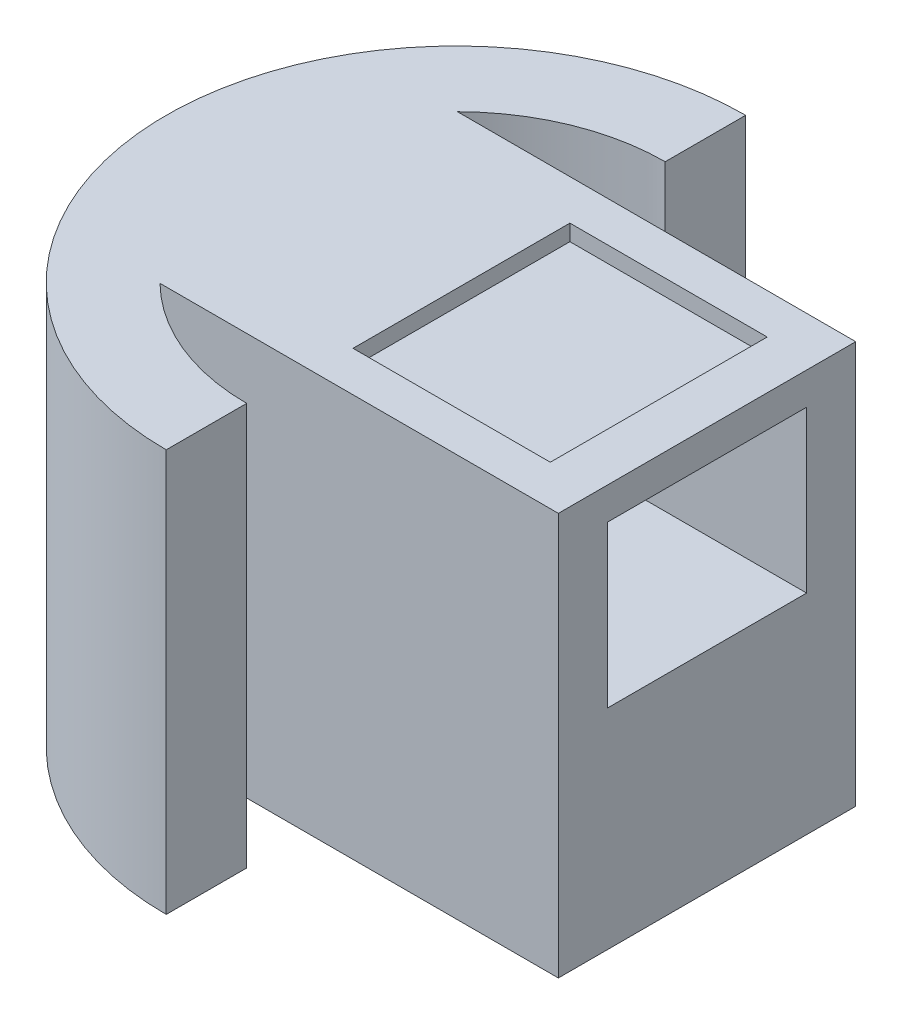
SolidWorks part; units mm, degrees
ref_plane "前基準面" through (0, 0, 0) normal (0, 0, 1) x (1, 0, 0)
ref_plane "上基準面" through (0, 0, 0) normal (0, 1, 0) x (1, 0, 0)
ref_plane "右基準面" through (0, 0, 0) normal (1, 0, 0) x (0, 0, -1)
sketch "草圖1" plane through (0, 0, 0) normal (0, 1, 0) x (1, 0, 0)
  line L0 (0, -1000) -> (0, 49000) construction
  arc A0 (0, 914.4) -> (0, -914.4) centre (0, 0) ccw
  dimension "D1" = 1828.8
extrude "伸長-薄件1" add sketch "草圖1" along normal blind 1270 thin thin type one direction reverse wall 254
sketch "草圖5" plane through (0, 1270, 0) normal (0, 1, 0) x (1, 0, 0)
  line L1 (-864.3979, -163.0846) -> (-792.1626, -163.0846)
  line L2 (-864.3979, -163.0846) -> (-864.3979, 175.7333)
  line L3 (-864.3979, 175.7333) -> (-792.1626, 175.7333)
  line L4 (-792.1626, -163.0846) -> (-792.1626, 175.7333)
extrude "填補1" add sketch "草圖5" against normal through all
sketch "草圖9" plane through (0, 1270, 0) normal (0, 1, 0) x (1, 0, 0)
  line L0 (-792.1626, -1061.7609) -> (-792.1626, 48938.2391) construction
  line L2 (-858.6021, -138.4881) -> (-792.1626, -138.4881)
  line L3 (-858.6021, -138.4881) -> (-858.6021, -258.1826)
  line L4 (-858.6021, -258.1826) -> (-792.1626, -258.1826)
  line L5 (-792.1626, -138.4881) -> (-792.1626, -258.1826)
extrude "填補2" add sketch "草圖9" against normal through all
sketch "第二分類" plane through (0, 0, 0) normal (0, 1, 0) x (1, 0, 0)
  line L1 (-792.4704, 339.6329) -> (792.4704, 339.6329)
  line L2 (-792.4704, 339.6329) -> (-792.4704, -339.6329)
  line L3 (-792.4704, -339.6329) -> (792.4704, -339.6329)
  line L4 (792.4704, 339.6329) -> (792.4704, -339.6329)
  line L5 (-792.4704, 339.6329) -> (792.4704, -339.6329) construction
  line L6 (-792.4704, -339.6329) -> (792.4704, 339.6329) construction
  point P0 (0, 0)
extrude "填料-伸長7" add sketch "第二分類" along normal blind 1270
sketch "草圖15" plane through (792.4704, 0, 0) normal (1, 0, 0) x (0, 0, -1)
  line L0 (-339.6329, 1270) -> (339.6329, 1270) construction
  line L1 (-339.6329, 1270) -> (-339.6329, 0) construction
  line L2 (-314.2329, 1168.4) -> (314.2329, 1168.4)
  line L3 (-314.2329, 1168.4) -> (-314.2329, 660.4)
  line L4 (-314.2329, 660.4) -> (314.2329, 660.4)
  line L5 (0, -1000) -> (0, 49000) construction
  line L6 (314.2329, 1168.4) -> (314.2329, 660.4)
  line L7 (-314.2329, 1168.4) -> (314.2329, 660.4) construction
  line L8 (-314.2329, 660.4) -> (314.2329, 1168.4) construction
  point P0 (0, 914.4)
  dimension "D1" = 25.4
  dimension "D2" = 508
  dimension "D3" = 101.6
extrude "除料-伸長1" cut sketch "草圖15" against normal blind 5080
sketch "草圖16" plane through (0, 1270, 0) normal (0, 1, 0) x (1, 0, 0)
  line L1 (792.4704, -339.6329) -> (-604.268, -339.6329)
  line L2 (792.4704, -339.6329) -> (792.4704, -469.2454)
  line L3 (792.4704, -469.2454) -> (-604.268, -469.2454)
  line L4 (-604.268, -339.6329) -> (-604.268, -469.2454)
extrude "填料-伸長8" add sketch "草圖16" against normal through all
sketch "草圖17" plane through (0, 1270, 0) normal (0, 1, 0) x (1, 0, 0)
  line L1 (792.4704, 339.6329) -> (-616.2692, 339.6329)
  line L2 (792.4704, 339.6329) -> (792.4704, 469.2454)
  line L3 (792.4704, 469.2454) -> (-616.2692, 469.2454)
  line L4 (-616.2692, 339.6329) -> (-616.2692, 469.2454)
extrude "填料-伸長9" add sketch "草圖17" against normal through all
sketch "草圖20" plane through (0, 1270, 0) normal (0, 1, 0) x (1, 0, 0)
  line L0 (-464.6901, -469.2454) -> (792.4704, -469.2454) construction
  line L1 (17.4108, -342.2454) -> (640.0704, -342.2454)
  line L2 (17.4108, -342.2454) -> (17.4108, 342.2454)
  line L3 (17.4108, 342.2454) -> (640.0704, 342.2454)
  line L4 (640.0704, -342.2454) -> (640.0704, 342.2454)
  line L5 (792.4704, 469.2454) -> (-464.6901, 469.2454) construction
  line L6 (792.4704, -469.2454) -> (792.4704, 469.2454) construction
  dimension "D1" = 127
  dimension "D2" = 127
  dimension "D3" = 152.4
extrude "除料-伸長2" cut sketch "草圖20" against normal blind 50.8
